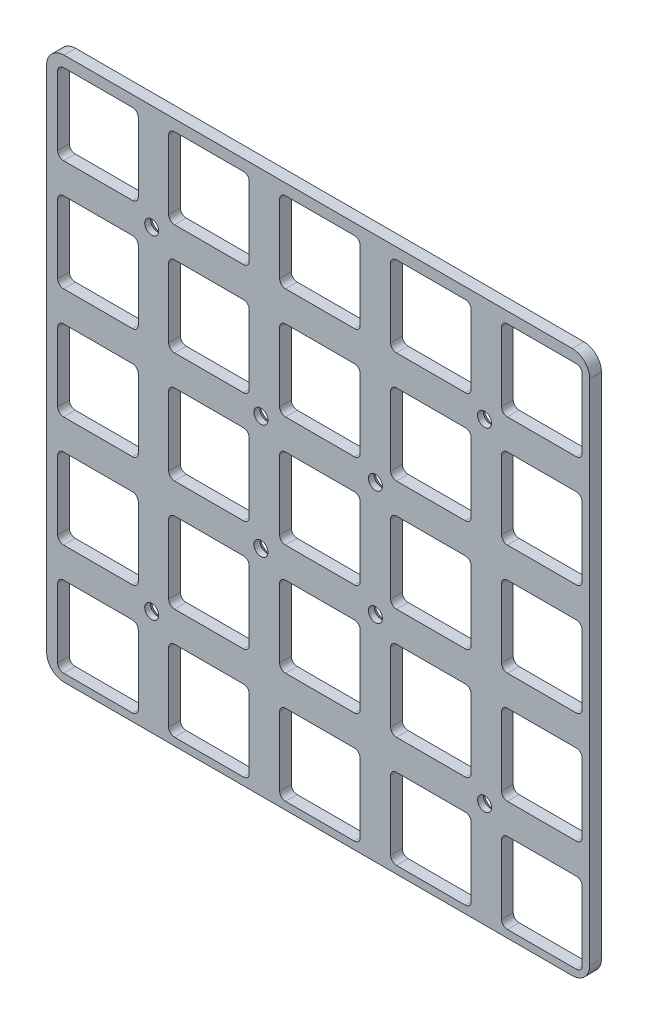
SolidWorks part; units mm, degrees
ref_plane "Front Plane" through (0, 0, 0) normal (0, 0, 1) x (1, 0, 0)
ref_plane "Top Plane" through (0, 0, 0) normal (0, 1, 0) x (1, 0, 0)
ref_plane "Right Plane" through (0, 0, 0) normal (1, 0, 0) x (0, 0, -1)
sketch "Sketch2" plane through (0, 0, 0) normal (0, 0, 1) x (1, 0, 0)
  line L0 (-43.5, 46.5) -> (43.5, 46.5)
  line L1 (-43.5, -47.5) -> (43.5, -47.5) construction
  line L2 (-47.5, -43.5) -> (-47.5, 43.5) construction
  line L3 (-43.5, 47.5) -> (43.5, 47.5) construction
  line L4 (47.5, -43.5) -> (47.5, 43.5) construction
  line L5 (-43.5, -43.5) -> (43.5, 43.5) construction
  line L6 (-43.5, 43.5) -> (43.5, -43.5) construction
  line L7 (46.5, -43.5) -> (46.5, 43.5)
  line L8 (-43.5, -46.5) -> (43.5, -46.5)
  line L9 (-46.5, -43.5) -> (-46.5, 43.5)
  line L10 (-25.6, 43.6) -> (-25.6, 31.8)
  line L11 (-43.6, 44.6) -> (-31.8, 44.6)
  line L12 (-44.6, 43.6) -> (-44.6, 31.8)
  line L13 (-43.6, 30.8) -> (-31.8, 30.8)
  line L14 (-30.8, 43.6) -> (-30.8, 31.8)
  line L15 (-24.6, 44.6) -> (-12.8, 44.6)
  line L16 (-11.8, 43.6) -> (-11.8, 31.8)
  line L17 (-24.6, 30.8) -> (-12.8, 30.8)
  line L18 (-6.6, 43.6) -> (-6.6, 31.8)
  line L19 (-5.6, 44.6) -> (6.2, 44.6)
  line L20 (7.2, 43.6) -> (7.2, 31.8)
  line L21 (-5.6, 30.8) -> (6.2, 30.8)
  line L22 (12.4, 43.6) -> (12.4, 31.8)
  line L23 (13.4, 44.6) -> (25.2, 44.6)
  line L24 (26.2, 43.6) -> (26.2, 31.8)
  line L25 (13.4, 30.8) -> (25.2, 30.8)
  line L26 (31.4, 43.6) -> (31.4, 31.8)
  line L27 (32.4, 44.6) -> (44.2, 44.6)
  line L28 (45.2, 43.6) -> (45.2, 31.8)
  line L29 (32.4, 30.8) -> (44.2, 30.8)
  line L30 (-25.6, 24.6) -> (-25.6, 12.8)
  line L31 (-24.6, 25.6) -> (-12.8, 25.6)
  line L32 (-11.8, 24.6) -> (-11.8, 12.8)
  line L33 (-24.6, 11.8) -> (-12.8, 11.8)
  line L34 (-6.6, 24.6) -> (-6.6, 12.8)
  line L35 (-5.6, 25.6) -> (6.2, 25.6)
  line L36 (7.2, 24.6) -> (7.2, 12.8)
  line L37 (-5.6, 11.8) -> (6.2, 11.8)
  line L38 (12.4, 24.6) -> (12.4, 12.8)
  line L39 (13.4, 25.6) -> (25.2, 25.6)
  line L40 (26.2, 24.6) -> (26.2, 12.8)
  line L41 (13.4, 11.8) -> (25.2, 11.8)
  line L42 (31.4, 24.6) -> (31.4, 12.8)
  line L43 (32.4, 25.6) -> (44.2, 25.6)
  line L44 (45.2, 24.6) -> (45.2, 12.8)
  line L45 (32.4, 11.8) -> (44.2, 11.8)
  line L46 (-25.6, 5.6) -> (-25.6, -6.2)
  line L47 (-24.6, 6.6) -> (-12.8, 6.6)
  line L48 (-11.8, 5.6) -> (-11.8, -6.2)
  line L49 (-24.6, -7.2) -> (-12.8, -7.2)
  line L50 (-6.6, 5.6) -> (-6.6, -6.2)
  line L51 (-5.6, 6.6) -> (6.2, 6.6)
  line L52 (7.2, 5.6) -> (7.2, -6.2)
  line L53 (-5.6, -7.2) -> (6.2, -7.2)
  line L54 (12.4, 5.6) -> (12.4, -6.2)
  line L55 (13.4, 6.6) -> (25.2, 6.6)
  line L56 (26.2, 5.6) -> (26.2, -6.2)
  line L57 (13.4, -7.2) -> (25.2, -7.2)
  line L58 (31.4, 5.6) -> (31.4, -6.2)
  line L59 (32.4, 6.6) -> (44.2, 6.6)
  line L60 (45.2, 5.6) -> (45.2, -6.2)
  line L61 (32.4, -7.2) -> (44.2, -7.2)
  line L62 (-25.6, -13.4) -> (-25.6, -25.2)
  line L63 (-24.6, -12.4) -> (-12.8, -12.4)
  line L64 (-11.8, -13.4) -> (-11.8, -25.2)
  line L65 (-24.6, -26.2) -> (-12.8, -26.2)
  line L66 (-6.6, -13.4) -> (-6.6, -25.2)
  line L67 (-5.6, -12.4) -> (6.2, -12.4)
  line L68 (7.2, -13.4) -> (7.2, -25.2)
  line L69 (-5.6, -26.2) -> (6.2, -26.2)
  line L70 (12.4, -13.4) -> (12.4, -25.2)
  line L71 (13.4, -12.4) -> (25.2, -12.4)
  line L72 (26.2, -13.4) -> (26.2, -25.2)
  line L73 (13.4, -26.2) -> (25.2, -26.2)
  line L74 (31.4, -13.4) -> (31.4, -25.2)
  line L75 (32.4, -12.4) -> (44.2, -12.4)
  line L76 (45.2, -13.4) -> (45.2, -25.2)
  line L77 (32.4, -26.2) -> (44.2, -26.2)
  line L78 (-25.6, -32.4) -> (-25.6, -44.2)
  line L79 (-24.6, -31.4) -> (-12.8, -31.4)
  line L80 (-11.8, -32.4) -> (-11.8, -44.2)
  line L81 (-24.6, -45.2) -> (-12.8, -45.2)
  line L82 (-6.6, -32.4) -> (-6.6, -44.2)
  line L83 (-5.6, -31.4) -> (6.2, -31.4)
  line L84 (7.2, -32.4) -> (7.2, -44.2)
  line L85 (-5.6, -45.2) -> (6.2, -45.2)
  line L86 (12.4, -32.4) -> (12.4, -44.2)
  line L87 (13.4, -31.4) -> (25.2, -31.4)
  line L88 (26.2, -32.4) -> (26.2, -44.2)
  line L89 (13.4, -45.2) -> (25.2, -45.2)
  line L90 (31.4, -32.4) -> (31.4, -44.2)
  line L91 (32.4, -31.4) -> (44.2, -31.4)
  line L92 (45.2, -32.4) -> (45.2, -44.2)
  line L93 (32.4, -45.2) -> (44.2, -45.2)
  line L94 (-44.6, 24.6) -> (-44.6, 12.8)
  line L95 (-43.6, 25.6) -> (-31.8, 25.6)
  line L96 (-30.8, 24.6) -> (-30.8, 12.8)
  line L97 (-43.6, 11.8) -> (-31.8, 11.8)
  line L98 (-44.6, 5.6) -> (-44.6, -6.2)
  line L99 (-43.6, 6.6) -> (-31.8, 6.6)
  line L100 (-30.8, 5.6) -> (-30.8, -6.2)
  line L101 (-43.6, -7.2) -> (-31.8, -7.2)
  line L102 (-44.6, -13.4) -> (-44.6, -25.2)
  line L103 (-43.6, -12.4) -> (-31.8, -12.4)
  line L104 (-30.8, -13.4) -> (-30.8, -25.2)
  line L105 (-43.6, -26.2) -> (-31.8, -26.2)
  line L106 (-44.6, -32.4) -> (-44.6, -44.2)
  line L107 (-43.6, -31.4) -> (-31.8, -31.4)
  line L108 (-30.8, -32.4) -> (-30.8, -44.2)
  line L109 (-43.6, -45.2) -> (-31.8, -45.2)
  line L110 (-44.6, 43.6) -> (-25.6, 43.6) construction
  line L111 (-44.6, 43.6) -> (-44.6, 24.6) construction
  arc A0 (-43.5, -47.5) -> (-47.5, -43.5) centre (-43.5, -43.5) cw construction
  arc A1 (43.5, -47.5) -> (47.5, -43.5) centre (43.5, -43.5) ccw construction
  arc A2 (43.5, 47.5) -> (47.5, 43.5) centre (43.5, 43.5) cw construction
  arc A3 (-47.5, 43.5) -> (-43.5, 47.5) centre (-43.5, 43.5) cw construction
  arc A4 (43.5, 46.5) -> (46.5, 43.5) centre (43.5, 43.5) cw
  arc A5 (43.5, -46.5) -> (46.5, -43.5) centre (43.5, -43.5) ccw
  arc A6 (-43.5, -46.5) -> (-46.5, -43.5) centre (-43.5, -43.5) cw
  arc A7 (-46.5, 43.5) -> (-43.5, 46.5) centre (-43.5, 43.5) cw
  arc A8 (-44.6, 31.8) -> (-43.6, 30.8) centre (-43.6, 31.8) ccw
  arc A9 (-31.8, 30.8) -> (-30.8, 31.8) centre (-31.8, 31.8) ccw
  arc A10 (-31.8, 44.6) -> (-30.8, 43.6) centre (-31.8, 43.6) cw
  arc A11 (-43.6, 44.6) -> (-44.6, 43.6) centre (-43.6, 43.6) ccw
  arc A12 (-24.6, 44.6) -> (-25.6, 43.6) centre (-24.6, 43.6) ccw
  arc A13 (-25.6, 31.8) -> (-24.6, 30.8) centre (-24.6, 31.8) ccw
  arc A14 (-12.8, 44.6) -> (-11.8, 43.6) centre (-12.8, 43.6) cw
  arc A15 (-12.8, 30.8) -> (-11.8, 31.8) centre (-12.8, 31.8) ccw
  arc A16 (-5.6, 44.6) -> (-6.6, 43.6) centre (-5.6, 43.6) ccw
  arc A17 (-6.6, 31.8) -> (-5.6, 30.8) centre (-5.6, 31.8) ccw
  arc A18 (6.2, 44.6) -> (7.2, 43.6) centre (6.2, 43.6) cw
  arc A19 (6.2, 30.8) -> (7.2, 31.8) centre (6.2, 31.8) ccw
  arc A20 (13.4, 44.6) -> (12.4, 43.6) centre (13.4, 43.6) ccw
  arc A21 (12.4, 31.8) -> (13.4, 30.8) centre (13.4, 31.8) ccw
  arc A22 (25.2, 44.6) -> (26.2, 43.6) centre (25.2, 43.6) cw
  arc A23 (25.2, 30.8) -> (26.2, 31.8) centre (25.2, 31.8) ccw
  arc A24 (32.4, 44.6) -> (31.4, 43.6) centre (32.4, 43.6) ccw
  arc A25 (31.4, 31.8) -> (32.4, 30.8) centre (32.4, 31.8) ccw
  arc A26 (44.2, 44.6) -> (45.2, 43.6) centre (44.2, 43.6) cw
  arc A27 (44.2, 30.8) -> (45.2, 31.8) centre (44.2, 31.8) ccw
  arc A28 (-24.6, 25.6) -> (-25.6, 24.6) centre (-24.6, 24.6) ccw
  arc A29 (-25.6, 12.8) -> (-24.6, 11.8) centre (-24.6, 12.8) ccw
  arc A30 (-12.8, 25.6) -> (-11.8, 24.6) centre (-12.8, 24.6) cw
  arc A31 (-12.8, 11.8) -> (-11.8, 12.8) centre (-12.8, 12.8) ccw
  arc A32 (-5.6, 25.6) -> (-6.6, 24.6) centre (-5.6, 24.6) ccw
  arc A33 (-6.6, 12.8) -> (-5.6, 11.8) centre (-5.6, 12.8) ccw
  arc A34 (6.2, 25.6) -> (7.2, 24.6) centre (6.2, 24.6) cw
  arc A35 (6.2, 11.8) -> (7.2, 12.8) centre (6.2, 12.8) ccw
  arc A36 (13.4, 25.6) -> (12.4, 24.6) centre (13.4, 24.6) ccw
  arc A37 (12.4, 12.8) -> (13.4, 11.8) centre (13.4, 12.8) ccw
  arc A38 (25.2, 25.6) -> (26.2, 24.6) centre (25.2, 24.6) cw
  arc A39 (25.2, 11.8) -> (26.2, 12.8) centre (25.2, 12.8) ccw
  arc A40 (32.4, 25.6) -> (31.4, 24.6) centre (32.4, 24.6) ccw
  arc A41 (31.4, 12.8) -> (32.4, 11.8) centre (32.4, 12.8) ccw
  arc A42 (44.2, 25.6) -> (45.2, 24.6) centre (44.2, 24.6) cw
  arc A43 (44.2, 11.8) -> (45.2, 12.8) centre (44.2, 12.8) ccw
  arc A44 (-24.6, 6.6) -> (-25.6, 5.6) centre (-24.6, 5.6) ccw
  arc A45 (-25.6, -6.2) -> (-24.6, -7.2) centre (-24.6, -6.2) ccw
  arc A46 (-12.8, 6.6) -> (-11.8, 5.6) centre (-12.8, 5.6) cw
  arc A47 (-12.8, -7.2) -> (-11.8, -6.2) centre (-12.8, -6.2) ccw
  arc A48 (-5.6, 6.6) -> (-6.6, 5.6) centre (-5.6, 5.6) ccw
  arc A49 (-6.6, -6.2) -> (-5.6, -7.2) centre (-5.6, -6.2) ccw
  arc A50 (6.2, 6.6) -> (7.2, 5.6) centre (6.2, 5.6) cw
  arc A51 (6.2, -7.2) -> (7.2, -6.2) centre (6.2, -6.2) ccw
  arc A52 (13.4, 6.6) -> (12.4, 5.6) centre (13.4, 5.6) ccw
  arc A53 (12.4, -6.2) -> (13.4, -7.2) centre (13.4, -6.2) ccw
  arc A54 (25.2, 6.6) -> (26.2, 5.6) centre (25.2, 5.6) cw
  arc A55 (25.2, -7.2) -> (26.2, -6.2) centre (25.2, -6.2) ccw
  arc A56 (32.4, 6.6) -> (31.4, 5.6) centre (32.4, 5.6) ccw
  arc A57 (31.4, -6.2) -> (32.4, -7.2) centre (32.4, -6.2) ccw
  arc A58 (44.2, 6.6) -> (45.2, 5.6) centre (44.2, 5.6) cw
  arc A59 (44.2, -7.2) -> (45.2, -6.2) centre (44.2, -6.2) ccw
  arc A60 (-24.6, -12.4) -> (-25.6, -13.4) centre (-24.6, -13.4) ccw
  arc A61 (-25.6, -25.2) -> (-24.6, -26.2) centre (-24.6, -25.2) ccw
  arc A62 (-12.8, -12.4) -> (-11.8, -13.4) centre (-12.8, -13.4) cw
  arc A63 (-12.8, -26.2) -> (-11.8, -25.2) centre (-12.8, -25.2) ccw
  arc A64 (-5.6, -12.4) -> (-6.6, -13.4) centre (-5.6, -13.4) ccw
  arc A65 (-6.6, -25.2) -> (-5.6, -26.2) centre (-5.6, -25.2) ccw
  arc A66 (6.2, -12.4) -> (7.2, -13.4) centre (6.2, -13.4) cw
  arc A67 (6.2, -26.2) -> (7.2, -25.2) centre (6.2, -25.2) ccw
  arc A68 (13.4, -12.4) -> (12.4, -13.4) centre (13.4, -13.4) ccw
  arc A69 (12.4, -25.2) -> (13.4, -26.2) centre (13.4, -25.2) ccw
  arc A70 (25.2, -12.4) -> (26.2, -13.4) centre (25.2, -13.4) cw
  arc A71 (25.2, -26.2) -> (26.2, -25.2) centre (25.2, -25.2) ccw
  arc A72 (32.4, -12.4) -> (31.4, -13.4) centre (32.4, -13.4) ccw
  arc A73 (31.4, -25.2) -> (32.4, -26.2) centre (32.4, -25.2) ccw
  arc A74 (44.2, -12.4) -> (45.2, -13.4) centre (44.2, -13.4) cw
  arc A75 (44.2, -26.2) -> (45.2, -25.2) centre (44.2, -25.2) ccw
  arc A76 (-24.6, -31.4) -> (-25.6, -32.4) centre (-24.6, -32.4) ccw
  arc A77 (-25.6, -44.2) -> (-24.6, -45.2) centre (-24.6, -44.2) ccw
  arc A78 (-12.8, -31.4) -> (-11.8, -32.4) centre (-12.8, -32.4) cw
  arc A79 (-12.8, -45.2) -> (-11.8, -44.2) centre (-12.8, -44.2) ccw
  arc A80 (-5.6, -31.4) -> (-6.6, -32.4) centre (-5.6, -32.4) ccw
  arc A81 (-6.6, -44.2) -> (-5.6, -45.2) centre (-5.6, -44.2) ccw
  arc A82 (6.2, -31.4) -> (7.2, -32.4) centre (6.2, -32.4) cw
  arc A83 (6.2, -45.2) -> (7.2, -44.2) centre (6.2, -44.2) ccw
  arc A84 (13.4, -31.4) -> (12.4, -32.4) centre (13.4, -32.4) ccw
  arc A85 (12.4, -44.2) -> (13.4, -45.2) centre (13.4, -44.2) ccw
  arc A86 (25.2, -31.4) -> (26.2, -32.4) centre (25.2, -32.4) cw
  arc A87 (25.2, -45.2) -> (26.2, -44.2) centre (25.2, -44.2) ccw
  arc A88 (32.4, -31.4) -> (31.4, -32.4) centre (32.4, -32.4) ccw
  arc A89 (31.4, -44.2) -> (32.4, -45.2) centre (32.4, -44.2) ccw
  arc A90 (44.2, -31.4) -> (45.2, -32.4) centre (44.2, -32.4) cw
  arc A91 (44.2, -45.2) -> (45.2, -44.2) centre (44.2, -44.2) ccw
  arc A92 (-43.6, 25.6) -> (-44.6, 24.6) centre (-43.6, 24.6) ccw
  arc A93 (-44.6, 12.8) -> (-43.6, 11.8) centre (-43.6, 12.8) ccw
  arc A94 (-31.8, 25.6) -> (-30.8, 24.6) centre (-31.8, 24.6) cw
  arc A95 (-31.8, 11.8) -> (-30.8, 12.8) centre (-31.8, 12.8) ccw
  arc A96 (-43.6, 6.6) -> (-44.6, 5.6) centre (-43.6, 5.6) ccw
  arc A97 (-44.6, -6.2) -> (-43.6, -7.2) centre (-43.6, -6.2) ccw
  arc A98 (-31.8, 6.6) -> (-30.8, 5.6) centre (-31.8, 5.6) cw
  arc A99 (-31.8, -7.2) -> (-30.8, -6.2) centre (-31.8, -6.2) ccw
  arc A100 (-43.6, -12.4) -> (-44.6, -13.4) centre (-43.6, -13.4) ccw
  arc A101 (-44.6, -25.2) -> (-43.6, -26.2) centre (-43.6, -25.2) ccw
  arc A102 (-31.8, -12.4) -> (-30.8, -13.4) centre (-31.8, -13.4) cw
  arc A103 (-31.8, -26.2) -> (-30.8, -25.2) centre (-31.8, -25.2) ccw
  arc A104 (-43.6, -31.4) -> (-44.6, -32.4) centre (-43.6, -32.4) ccw
  arc A105 (-44.6, -44.2) -> (-43.6, -45.2) centre (-43.6, -44.2) ccw
  arc A106 (-31.8, -31.4) -> (-30.8, -32.4) centre (-31.8, -32.4) cw
  arc A107 (-31.8, -45.2) -> (-30.8, -44.2) centre (-31.8, -44.2) ccw
  point P0 (0, 0)
  dimension "D1" = 4
  dimension "D4" = 1
  dimension "D2" = 95
  dimension "D5" = 13.8
  dimension "D6" = 2.9
  dimension "D9" = 90
  dimension "D10" = 19
  dimension "D11" = 19
  dimension "D3" = 1
  dimension "D7" = 5
  dimension "D8" = 5
extrude "Boss-Extrude1" add sketch "Sketch2" along normal blind 2
sketch "Sketch3" plane through (0, 0, 0) normal (0, 0, -1) x (-1, 0, 0)
  line L0 (43.5, 43.5) -> (-43.5, -43.5) construction
  line L1 (43.5, 43.5) -> (-43.5, -43.5) construction
  point P2 (-28.5, -28.5)
  point P26 (-9.8, -9.8)
  point P32 (-28.5, 28.5)
  point P33 (-9.8, 9.8)
  point P34 (28.5, 28.5)
  point P35 (9.8, 9.8)
  point P36 (28.5, -28.5)
  point P37 (9.8, -9.8)
  dimension "D1" = 28.5
  dimension "D2" = 9.8
  dimension "D3" = 4
hole_wizard "CSK for M2 Flat Head Machine Screw5" positions "Sketch3" profile "Sketch7" countersink size "M2" standard "ANSI Metric" end condition through all
sketch "Sketch7" plane through (-9.8, -9.8, 0) normal (1, 0, 0) x (0, 1, 0)
  line L0 (0, 0) -> (0, 2)
  line L1 (0, 2) -> (1.2, 2)
  line L2 (1.2, 2) -> (1.2, 1)
  line L3 (1.2, 1) -> (2.2, 0)
  line L5 (2.2, 0) -> (0, 0)
  line L6 (-1.2, 1) -> (-2.2, 0) construction
  line L11 (0, -6.35) -> (0, 107.95) construction
  dimension "Thru Hole Dia." = 2.4
  dimension "Thru Hole Depth" = 2
  dimension "Near C'Sink Dia." = 4.4
  dimension "Near C'Sink Angle" = 90
